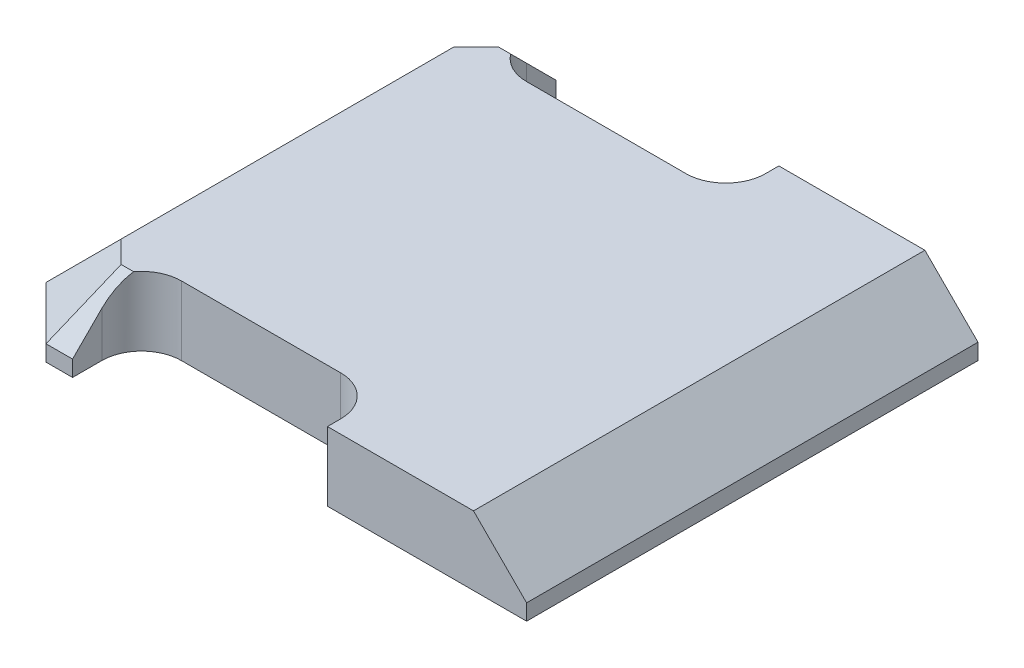
SolidWorks part; units mm, degrees
material "ABS"
ref_plane "Front Plane" through (0, 0, 0) normal (0, 0, 1) x (1, 0, 0)
ref_plane "Top Plane" through (0, 0, 0) normal (0, 1, 0) x (1, 0, 0)
ref_plane "Right Plane" through (0, 0, 0) normal (1, 0, 0) x (0, 0, -1)
sketch "Sketch1" plane through (0, 0, 0) normal (0, 1, 0) x (1, 0, 0)
  line L1 (-97.5, 85) -> (97.5, 85)
  line L2 (-97.5, 85) -> (-97.5, -85)
  line L3 (-97.5, -85) -> (97.5, -85)
  line L4 (97.5, 85) -> (97.5, -85)
  line L5 (-97.5, 85) -> (97.5, -85) construction
  line L6 (-97.5, -85) -> (97.5, 85) construction
  point P0 (0, 0)
  dimension "D1" = 195
  dimension "D2" = 170
extrude "Boss-Extrude1" add sketch "Sketch1" along normal blind 26
sketch "Sketch2" plane through (0, 26, 0) normal (0, 1, 0) x (1, 0, 0)
  line L0 (-97.5, -85) -> (-67.5, -85) construction
  line L1 (-97.5, -85) -> (97.5, -85) construction
  line L2 (0, 0) -> (-97.5, 0) construction
  line L3 (-67.5, -85) -> (22.5, -85)
  line L4 (-67.5, -85) -> (-67.5, -65)
  line L5 (-67.5, -65) -> (22.5, -65)
  line L6 (22.5, -85) -> (22.5, -65)
  line L7 (-97.5, 85) -> (-97.5, -85) construction
  line L8 (-67.5, 65) -> (22.5, 65)
  line L9 (22.5, 85) -> (22.5, 65)
  line L10 (-67.5, 85) -> (22.5, 85)
  line L11 (-67.5, 85) -> (-67.5, 65)
  dimension "D1" = 30
  dimension "D2" = 90
  dimension "D3" = 20
extrude "Cut-Extrude1" cut sketch "Sketch2" against normal through all
fillet "Fillet1" radius 15 4 edges at (22.5, 13, -65) (-67.5, 13, -65) (-67.5, 13, 65) (22.5, 13, 65)
sketch "Sketch3" plane through (0, 26, 0) normal (0, 1, 0) x (1, 0, 0)
  line L0 (0, 0) -> (-97.5, 0) construction
  line L1 (-67.5, 85) -> (-97.5, 85)
  line L2 (-67.5, 85) -> (-67.5, 91)
  line L3 (-67.5, 91) -> (-97.5, 91)
  line L4 (-97.5, 85) -> (-97.5, 91)
  line L5 (-97.5, 85) -> (-97.5, -85) construction
  line L6 (-67.5, -91) -> (-97.5, -91)
  line L7 (-97.5, -85) -> (-97.5, -91)
  line L8 (-67.5, -85) -> (-97.5, -85)
  line L9 (-67.5, -85) -> (-67.5, -91)
  dimension "D1" = 6
extrude "Boss-Extrude2" add sketch "Sketch3" against normal up to surface (26 mm away) up to face at (-16.875, 0, 0)
chamfer "Chamfer1" distance 20 angle 45 2 edges at (-97.5, 13, 91) (-97.5, 13, -91)
chamfer "Chamfer2" distance 20 angle 45 5 edges at (-72.5, 26, 91) (-72.5, 26, -91) (-97.5, 26, 0) (-87.5, 26, 81) (-87.5, 26, -81)
chamfer "Chamfer3" distance 20 angle 45 1 edges at (97.5, 26, 0)
sketch "Sketch4" plane through (-97.5, 0, 0) normal (-1, 0, 0) x (0, 0, 1)
  line L0 (0.1107, 11) -> (0, 0) construction
  line L1 (-4.3893, 15.5) -> (4.6107, 15.5)
  line L2 (-4.3893, 15.5) -> (-4.3893, 6.5)
  line L3 (-4.3893, 6.5) -> (4.6107, 6.5)
  line L4 (4.6107, 15.5) -> (4.6107, 6.5)
  line L5 (-4.3893, 15.5) -> (4.6107, 6.5) construction
  line L6 (-4.3893, 6.5) -> (4.6107, 15.5) construction
  point P0 (0.1107, 11)
  dimension "D1" = 9
  dimension "D2" = 9
  dimension "D3" = 11
extrude "Cut-Extrude2" cut sketch "Sketch4" against normal blind 20
